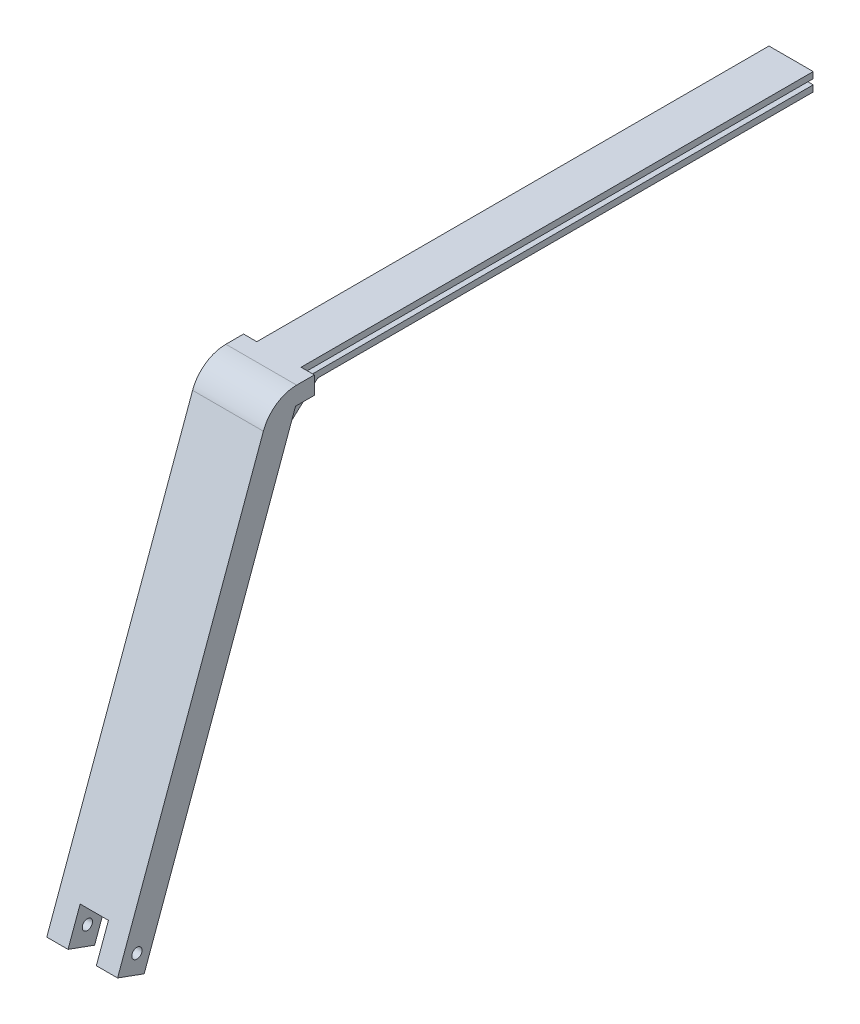
SolidWorks part; units mm, degrees
ref_plane "Front Plane" through (0, 0, 0) normal (0, 0, 1) x (1, 0, 0)
ref_plane "Top Plane" through (0, 0, 0) normal (0, 1, 0) x (1, 0, 0)
ref_plane "Right Plane" through (0, 0, 0) normal (1, 0, 0) x (0, 0, -1)
sketch "Sketch2" plane through (0, 0, 0) normal (1, 0, 0) x (0, 0, -1)
  line L0 (36.0729, 122.5) -> (-51.2799, -117.5)
  line L1 (-51.2799, -117.5) -> (-51.2799, -192)
  line L5 (-42.7665, -117.5) -> (42.7665, 117.5)
  line L6 (192.7665, 122.5) -> (36.0729, 122.5)
  line L7 (-42.7665, -117.5) -> (-35.6799, -117.5)
  line L9 (-39.6799, -151.5) -> (-46.2799, -151.5)
  line L10 (-46.2799, -151.5) -> (-46.2799, -192)
  line L13 (-35.6799, -117.5) -> (-35.6799, -192)
  line L14 (-35.6799, -192) -> (-39.6799, -192)
  line L15 (-39.6799, -192) -> (-39.6799, -151.5)
  line L16 (-51.2799, -192) -> (-46.2799, -192)
  line L18 (192.7665, 122.5) -> (192.7665, 117.5)
  line L19 (192.7665, 117.5) -> (42.7665, 117.5)
  dimension "D1" = 34
  dimension "D2" = 4
  dimension "D3" = 5
  dimension "D4" = 6.6
  dimension "D5" = 150
  dimension "D6" = 5
  dimension "D7" = 40.5
  dimension "D9" = 240
  dimension "D10" = 8
  dimension "D11" = 70
extrude "Boss-Extrude1" add sketch "Sketch2" along normal mid plane 20
chamfer "Chamfer1" distance 10 angle 45 1 edges at (0, -117.5, 42.7665) first distance on face at (0, -117.5, 39.2232)
sketch "Sketch6" plane through (10, 0, 0) normal (1, 0, 0) x (0, 0, -1)
  line L0 (-51.2799, -180) -> (-66.2799, -192)
  line L1 (-66.2799, -192) -> (-51.2799, -192)
  line L2 (-51.2799, -192) -> (-51.2799, -180)
  line L3 (-51.2799, -117.5) -> (-51.2799, -192) construction
  line L4 (-35.6799, -192) -> (-20.6799, -192)
  line L5 (-20.6799, -192) -> (-35.6799, -180)
  line L6 (-35.6799, -192) -> (-35.6799, -114.5866) construction
  line L7 (-35.6799, -180) -> (-35.6799, -192)
  dimension "D1" = 15
  dimension "D2" = 12
extrude "Boss-Extrude2" add sketch "Sketch6" against normal up to vertex (20 mm away) up to point (-10, -192, 51.2799)
sketch "Sketch7" plane through (0, -192, 0) normal (0, -1, 0) x (-1, 0, 0)
  line L0 (0, -66.2799) -> (0, -46.2799) construction
  line L1 (10, -66.2799) -> (-10, -66.2799) construction
  line L2 (-10, -46.2799) -> (10, -46.2799) construction
  line L3 (0, -20.6799) -> (0, -39.6799) construction
  line L4 (10, -20.6799) -> (-10, -20.6799) construction
  line L5 (-10, -39.6799) -> (10, -39.6799) construction
  circle A0 centre (0, -56.2799) radius 1.5
  circle A1 centre (0, -30.1799) radius 1.5
  dimension "D1" = 3
  dimension "D2" = 3
extrude "Cut-Extrude1" cut sketch "Sketch7" against normal blind 20
ref_plane "Plane1" through (0, -187, 0) normal (0, -1, 0) x (-1, 0, 0)
sketch "Sketch9" plane through (0, -187, 0) normal (0, -1, 0) x (-1, 0, 0)
  line L1 (2.75, -57.8676) -> (2.75, -54.6922)
  line L2 (2.75, -54.6922) -> (0, -53.1045)
  line L3 (0, -53.1045) -> (-2.75, -54.6922)
  line L4 (-2.75, -54.6922) -> (-2.75, -57.8676)
  line L5 (-2.75, -57.8676) -> (0, -59.4554)
  line L6 (0, -59.4554) -> (2.75, -57.8676)
  line L7 (2.75, -31.7676) -> (2.75, -28.5922)
  line L8 (2.75, -28.5922) -> (0, -27.0045)
  line L9 (0, -27.0045) -> (-2.75, -28.5922)
  line L10 (-2.75, -28.5922) -> (-2.75, -31.7676)
  line L11 (-2.75, -31.7676) -> (0, -33.3554)
  line L12 (0, -33.3554) -> (2.75, -31.7676)
  circle A0 centre (0, -56.2799) radius 2.75 construction
  circle A1 centre (0, -30.1799) radius 2.75 construction
  dimension "D1" = 5.5
  dimension "D2" = 5.5
extrude "Cut-Extrude3" cut sketch "Sketch9" against normal blind 20
fillet "Fillet5" radius 20 1 edges at (0, -117.5, 51.2799)
fillet "Fillet6" radius 10 1 edges at (0, 122.5, -36.0729)
sketch "Sketch10" plane through (10, 0, 0) normal (1, 0, 0) x (0, 0, -1)
  line L0 (-51.2799, -180) -> (-66.2799, -192) construction
  line L1 (-66.2799, -192) -> (-60.9799, -192)
  line L2 (-66.2799, -192) -> (-66.2799, -187.76)
  line L3 (-66.2799, -187.76) -> (-60.9799, -187.76)
  line L4 (-60.9799, -192) -> (-60.9799, -187.76)
  line L6 (-43.4799, -150) -> (-43.4799, -190.5) construction
  line L8 (-25.9799, -192) -> (-25.9799, -187.76)
  line L9 (-20.6799, -187.76) -> (-25.9799, -187.76)
  line L10 (-20.6799, -192) -> (-20.6799, -187.76)
  line L11 (-20.6799, -192) -> (-25.9799, -192)
  dimension "D1" = 35
extrude "Cut-Extrude4" cut sketch "Sketch10" against normal through all
sketch "Sketch11" plane through (0, 122.5, 0) normal (0, 1, 0) x (1, 0, 0)
  line L5 (-10, 43.075) -> (10, 43.075) construction
  line L6 (-10, 192.7665) -> (-6.25, 192.7665)
  line L7 (-10, 192.7665) -> (-10, 48.075)
  line L8 (-10, 48.075) -> (-6.25, 48.075)
  line L9 (-6.25, 192.7665) -> (-6.25, 48.075)
  line L10 (10, 192.7665) -> (6.25, 192.7665)
  line L11 (10, 192.7665) -> (10, 48.075)
  line L12 (10, 48.075) -> (6.25, 48.075)
  line L13 (6.25, 192.7665) -> (6.25, 48.075)
  dimension "D1" = 12.5
  dimension "D2" = 5
extrude "Cut-Extrude5" cut sketch "Sketch11" against normal through all
sketch "Sketch13" plane through (6.25, 0, 0) normal (1, 0, 0) x (0, 0, -1)
  line L0 (52.7665, 117.5) -> (37.7665, 103.7626)
  line L1 (192.7665, 117.5) -> (48.075, 117.5) construction
  line L2 (-40.098, -110.1685) -> (42.7665, 117.5) construction
  line L3 (37.7665, 103.7626) -> (42.7665, 117.5)
  line L4 (42.7665, 117.5) -> (52.7665, 117.5)
  dimension "D1" = 10
  dimension "D2" = 15
extrude "Boss-Extrude4" add sketch "Sketch13" against normal blind 12.5
sketch "Sketch12" plane through (0, 0, -192.7665) normal (0, 0, -1) x (-1, 0, 0)
  line L0 (-6.25, 117.5) -> (-6.25, 122.5) construction
  line L1 (-6.25, 120.75) -> (-4.25, 120.75)
  line L2 (-6.25, 120.75) -> (-6.25, 119.25)
  line L3 (-6.25, 119.25) -> (-4.25, 119.25)
  line L4 (-4.25, 120.75) -> (-4.25, 119.25)
  line L5 (0, 122.5) -> (0, 117.5) construction
  line L6 (-6.25, 122.5) -> (6.25, 122.5) construction
  line L7 (-6.25, 117.5) -> (6.25, 117.5) construction
  line L8 (4.25, 120.75) -> (4.25, 119.25)
  line L9 (6.25, 119.25) -> (4.25, 119.25)
  line L10 (6.25, 120.75) -> (6.25, 119.25)
  line L11 (6.25, 120.75) -> (4.25, 120.75)
  line L12 (-6.25, 122.5) -> (-6.25, 120.75) construction
  line L13 (-6.25, 117.5) -> (-6.25, 119.25) construction
  dimension "D1" = 1.75
  dimension "D2" = 1.5
  dimension "D3" = 2
extrude "Cut-Extrude6" cut sketch "Sketch12" against normal up to vertex (144.6915 mm away) up to point (10, 122.5, -48.075)
sketch "Sketch14" plane through (10, 0, 0) normal (1, 0, 0) x (0, 0, -1)
  line L0 (-7.5175, 2.7362) -> (0, 0)
  line L1 (33.6781, 115.9202) -> (-50.0738, -114.1861) construction
  line L2 (-7.5175, 2.7362) -> (-80.4546, -132.9976)
  line L3 (-80.4546, -132.9976) -> (-80.4546, -210.6524)
  line L4 (-80.4546, -210.6524) -> (0, -210.6524)
  line L5 (0, -210.6524) -> (0, 0)
extrude "Cut-Extrude7" cut sketch "Sketch14" against normal through all
sketch "Sketch15" plane through (0, 2.7362, 7.5175) normal (0, 0.342, 0.9397) x (1, 0, 0)
  line L0 (-10, 0) -> (10, 0) construction
  line L1 (-4, 0) -> (4, 0)
  line L2 (-4, 0) -> (-4, 10)
  line L3 (-4, 10) -> (4, 10)
  line L4 (4, 0) -> (4, 10)
  point P6 (7.9695, 0)
  point P7 (0, 0)
  dimension "D1" = 8
  dimension "5" = 10
extrude "Cut-Extrude8" cut sketch "Sketch15" against normal through all
sketch "Sketch16" plane through (10, 0, 0) normal (1, 0, 0) x (0, 0, -1)
  line L0 (-3.7588, 1.3681) -> (-0.3386, 10.765) construction
  line L1 (0, 0) -> (-7.5175, 2.7362) construction
  line L2 (33.6781, 115.9202) -> (-7.5175, 2.7362) construction
  circle A0 centre (-2.0487, 6.0665) radius 1.45
  point P6 (0, 10.6459)
  point P7 (0, 0)
  point P8 (2.4041, 9.2433)
  dimension "D2" = 2.9
  dimension "D1" = 10
extrude "Cut-Extrude9" cut sketch "Sketch16" against normal through all
